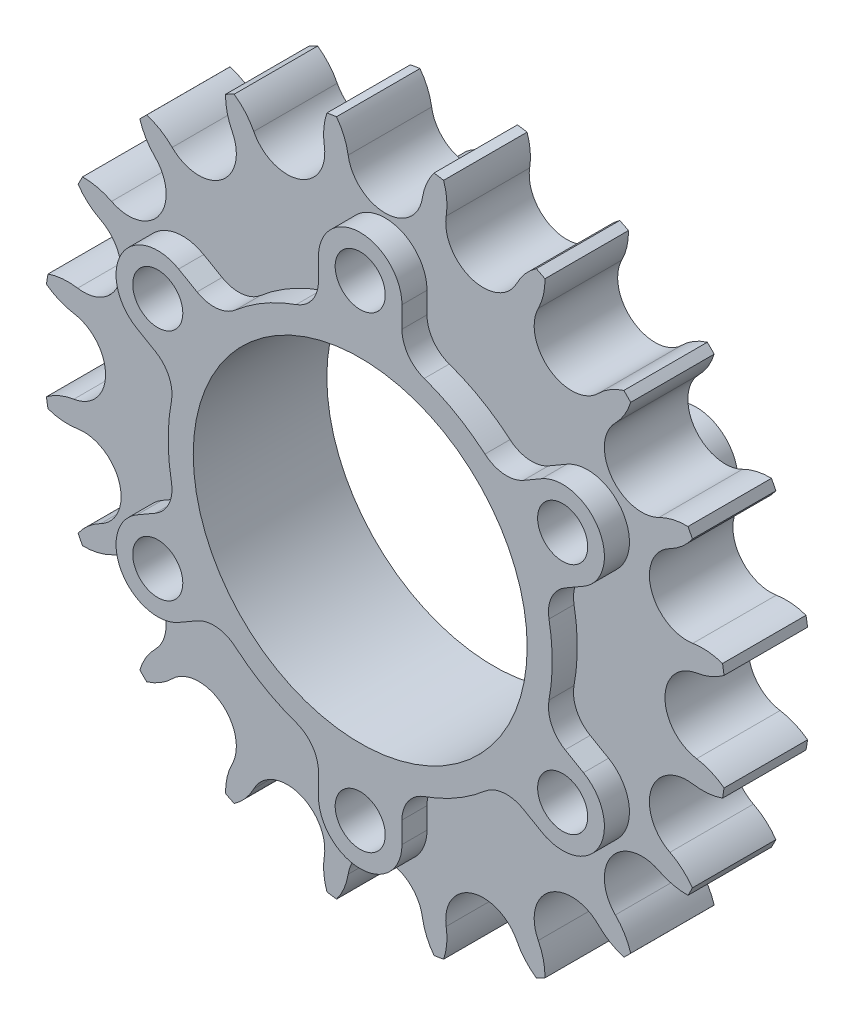
SolidWorks part; units mm, degrees
ref_plane "Front Plane" through (0, 0, 0) normal (0, 0, 1) x (1, 0, 0)
ref_plane "Top Plane" through (0, 0, 0) normal (0, 1, 0) x (1, 0, 0)
ref_plane "Right Plane" through (0, 0, 0) normal (1, 0, 0) x (0, 0, -1)
sketch "Sketch1" plane through (0, 0, 0) normal (0, 0, 1) x (1, 0, 0)
  circle A0 centre (0, 0) radius 20.5
  circle A1 centre (0, 0) radius 10
  dimension "D1" = 41
  dimension "D2" = 20
extrude "Boss-Extrude1" add sketch "Sketch1" along normal mid plane 5 contours A0 | A1
sketch "Sketch2" plane through (0, 0, 0) normal (0, 0, 1) x (1, 0, 0)
  line L0 (2.5, 14) -> (2.5, 12.7279)
  line L1 (-2.5, 14) -> (-2.5, 12.7279)
  line L2 (10.8744, 9.1651) -> (9.7727, 8.529)
  line L3 (13.3744, 4.8349) -> (12.2727, 4.1989)
  line L4 (13.3744, -4.8349) -> (12.2727, -4.1989)
  line L5 (10.8744, -9.1651) -> (9.7727, -8.529)
  line L6 (2.5, -14) -> (2.5, -12.7279)
  line L7 (-2.5, -14) -> (-2.5, -12.7279)
  line L8 (-10.8744, -9.1651) -> (-9.7727, -8.529)
  line L9 (-13.3744, -4.8349) -> (-12.2727, -4.1989)
  line L10 (-13.3744, 4.8349) -> (-12.2727, 4.1989)
  line L11 (-10.8744, 9.1651) -> (-9.7727, 8.529)
  arc A0 (2.5, 14) -> (-2.5, 14) centre (0, 14) ccw
  arc A1 (-3.8333, 10.8423) -> (-7.473, 8.7409) centre (0, 0) ccw
  arc A2 (13.3744, 4.8349) -> (10.8744, 9.1651) centre (12.1244, 7) ccw
  arc A3 (10.8744, -9.1651) -> (13.3744, -4.8349) centre (12.1244, -7) ccw
  arc A4 (-2.5, -14) -> (2.5, -14) centre (0, -14) ccw
  arc A5 (-13.3744, -4.8349) -> (-10.8744, -9.1651) centre (-12.1244, -7) ccw
  arc A6 (-10.8744, 9.1651) -> (-13.3744, 4.8349) centre (-12.1244, 7) ccw
  arc A7 (-11.3064, 2.1014) -> (-11.3064, -2.1014) centre (0, 0) ccw
  arc A8 (-7.473, -8.7409) -> (-3.8333, -10.8423) centre (0, 0) ccw
  arc A9 (3.8333, -10.8423) -> (7.473, -8.7409) centre (0, 0) ccw
  arc A10 (11.3064, -2.1014) -> (11.3064, 2.1014) centre (0, 0) ccw
  arc A11 (7.473, 8.7409) -> (3.8333, 10.8423) centre (0, 0) ccw
  arc A12 (2.5, 12.7279) -> (3.8333, 10.8423) centre (4.5, 12.7279) ccw
  arc A13 (9.7727, 8.529) -> (7.473, 8.7409) centre (8.7727, 10.2611) cw
  arc A14 (12.2727, 4.1989) -> (11.3064, 2.1014) centre (13.2727, 2.4668) ccw
  arc A15 (12.2727, -4.1989) -> (11.3064, -2.1014) centre (13.2727, -2.4668) cw
  arc A16 (9.7727, -8.529) -> (7.473, -8.7409) centre (8.7727, -10.2611) ccw
  arc A17 (2.5, -12.7279) -> (3.8333, -10.8423) centre (4.5, -12.7279) cw
  arc A18 (-2.5, -12.7279) -> (-3.8333, -10.8423) centre (-4.5, -12.7279) ccw
  arc A19 (-9.7727, -8.529) -> (-7.473, -8.7409) centre (-8.7727, -10.2611) cw
  arc A20 (-12.2727, -4.1989) -> (-11.3064, -2.1014) centre (-13.2727, -2.4668) ccw
  arc A21 (-12.2727, 4.1989) -> (-11.3064, 2.1014) centre (-13.2727, 2.4668) cw
  arc A22 (-9.7727, 8.529) -> (-7.473, 8.7409) centre (-8.7727, 10.2611) ccw
  arc A23 (-2.5, 12.7279) -> (-3.8333, 10.8423) centre (-4.5, 12.7279) cw
  circle A24 centre (0, 0) radius 10
  point P35 (0, 0)
  dimension "D1" = 5
  dimension "D2" = 23
  dimension "D5" = 2
  dimension "D3" = 14
  dimension "D4" = 6
extrude "Boss-Extrude2" add sketch "Sketch2" along normal mid plane 8
sketch "Sketch3" plane through (0, 0, 4) normal (0, 0, 1) x (1, 0, 0)
  circle A0 centre (0, 14) radius 1.5
  circle A1 centre (12.1244, 7) radius 1.5
  circle A2 centre (12.1244, -7) radius 1.5
  circle A3 centre (0, -14) radius 1.5
  circle A4 centre (-12.1244, -7) radius 1.5
  circle A5 centre (-12.1244, 7) radius 1.5
  point P15 (0, 0)
  dimension "D1" = 3
  dimension "D2" = 6
extrude "Cut-Extrude1" cut sketch "Sketch3" against normal blind 10
sketch "Sketch4" plane through (0, 0, 0) normal (0, 0, 1) x (1, 0, 0)
  line L0 (0, 0) -> (0, 19) construction
  line L1 (0, 19) -> (5.8713, 18.0701) construction
  line L2 (5.8713, 18.0701) -> (0, 0) construction
  line L3 (-5.8713, 18.0701) -> (0, 0) construction
  circle A0 centre (0, 19) radius 3.6945
  circle A1 centre (5.8713, 18.0701) radius 3.6945
  circle A2 centre (5.8713, 18.0701) radius 2.25
  circle A3 centre (0, 19) radius 2.25
  circle A4 centre (-5.8713, 18.0701) radius 2.25
  circle A5 centre (-5.8713, 18.0701) radius 3.6945
  dimension "D3" = 4.5
  dimension "D1" = 18
  dimension "D2" = 19
extrude "Cut-Extrude2" cut sketch "Sketch4" against normal through all both and the other way through all contours A3 | A0 A5 A3 A1 region at (0, 21.2957, 0) region at (0, 19, 0)
pattern_circular "CirPattern1" count 20 over 360 about axis through (0, 0, 2.5) along (0, 0, 1) of "Cut-Extrude2"
